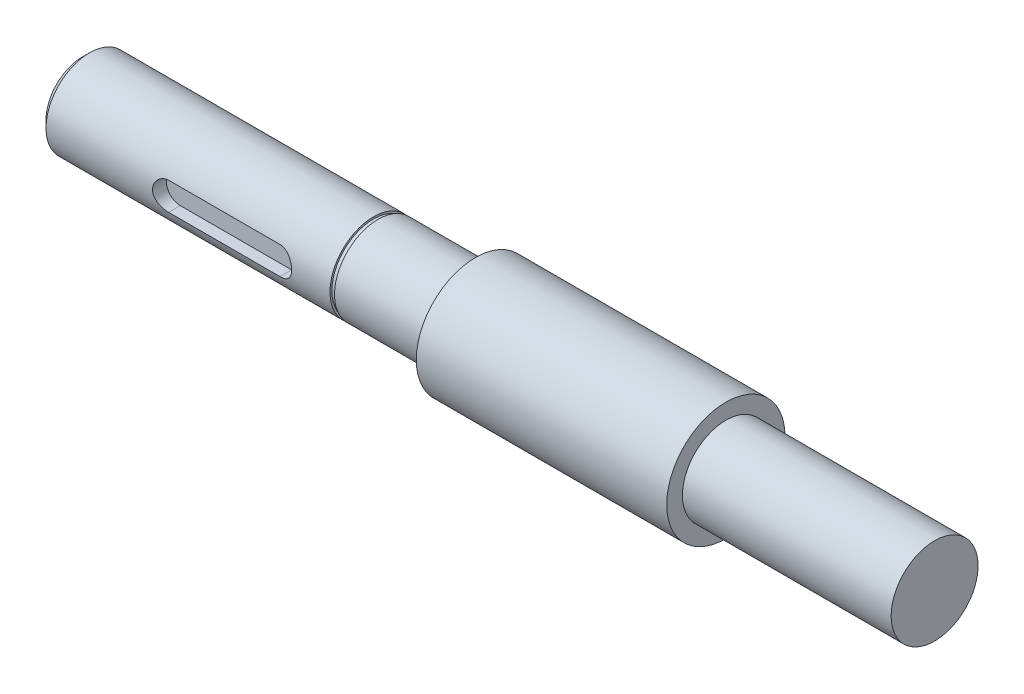
SolidWorks part; units mm, degrees
ref_plane "Ön Düzlem" through (0, 0, 0) normal (0, 0, 1) x (1, 0, 0)
ref_plane "Üst Düzlem" through (0, 0, 0) normal (0, 1, 0) x (1, 0, 0)
ref_plane "Sağ Düzlem" through (0, 0, 0) normal (1, 0, 0) x (0, 0, -1)
sketch "Çizim1" plane through (0, 0, 0) normal (0, 0, 1) x (1, 0, 0)
  line L0 (0, 0) -> (84.0966, 0) construction
  line L1 (0, 0) -> (-61, 0)
  line L2 (-61, 0) -> (-61, 10.5)
  line L3 (1.9449, 12.5) -> (51.9449, 12.5)
  line L4 (51.9449, 12.5) -> (51.9449, 17)
  line L5 (51.9449, 17) -> (123.9449, 17)
  line L7 (0, 0) -> (123.9449, 0)
  line L8 (-59, 12.5) -> (1.9449, 12.5)
  line L9 (-61, 10.5) -> (-59, 12.5)
  line L10 (123.9449, 0) -> (183.9449, 0) construction
  line L11 (183.9449, 0) -> (183.9449, 12.5)
  line L12 (123.9449, 17) -> (123.9449, 12.5)
  line L13 (123.9449, 12.5) -> (183.9449, 12.5)
  line L14 (123.9449, 0) -> (183.9449, 0)
  point P9 (-61, 12.5)
  dimension "D1" = 12.5
  dimension "D2" = 50
  dimension "D3" = 17
  dimension "D4" = 72
  dimension "D5" = 61
  dimension "D6" = 12.5
revolve "Döndür1" add sketch "Çizim1" angle 360 about L0
sketch "Çizim2" plane through (0, 0, 0) normal (0, 1, 0) x (1, 0, 0)
  line L1 (22.64, -13.7786) -> (23.94, -13.7786)
  line L2 (22.64, -13.7786) -> (22.64, -11.95)
  line L3 (22.64, -11.95) -> (23.94, -11.95)
  line L4 (23.94, -13.7786) -> (23.94, -11.95)
  line L5 (0, 0) -> (37.4637, 0) construction
  dimension "D2" = 1.3
  dimension "D3" = 11.95
revolve "Kes-Döndür1" cut sketch "Çizim2" angle 360 about L5
sketch "Çizim3" plane through (0, 0, 0) normal (0, 0, 1) x (1, 0, 0)
  line L0 (-24.3917, 0) -> (7.6083, 0) construction
  line L1 (-24.3917, 4) -> (7.6083, 4)
  line L2 (-24.3917, -4) -> (7.6083, -4)
  arc A0 (-24.3917, 4) -> (-24.3917, -4) centre (-24.3917, 0) ccw
  arc A1 (7.6083, -4) -> (7.6083, 4) centre (7.6083, 0) ccw
  point P3 (-8.3917, 0)
  dimension "D1" = 4
  dimension "D2" = 40
extrude "Kes-Ekstrüzyon1" cut sketch "Çizim3" along normal blind 10 from offset 8.5
extrude "Kes-Ekstrüzyon2" cut sketch "Çizim3<2>" against normal blind 10 from offset 8.5 offset against normal yes
sketch "Çizim3<2>" plane through (0, 0, 0) normal (0, 0, 1) x (1, 0, 0) same geometry as "Çizim3"
